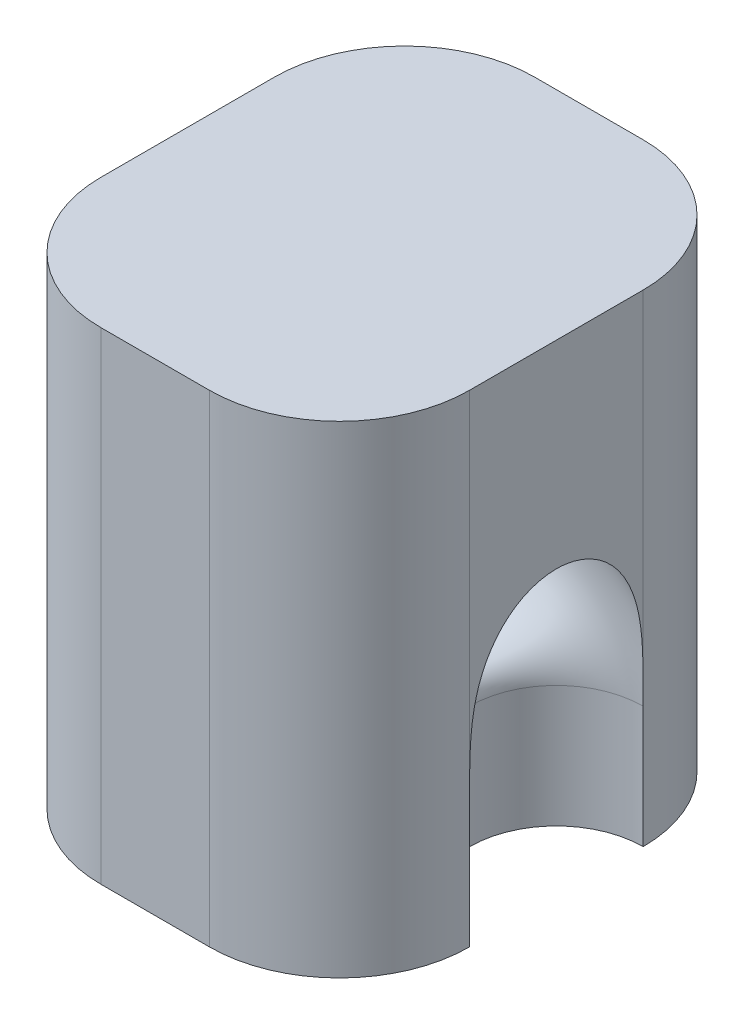
SolidWorks part; units mm, degrees
ref_plane "Front Plane" through (0, 0, 0) normal (0, 0, 1) x (1, 0, 0)
ref_plane "Top Plane" through (0, 0, 0) normal (0, 1, 0) x (1, 0, 0)
ref_plane "Right Plane" through (0, 0, 0) normal (1, 0, 0) x (0, 0, -1)
sketch "Sketch1" plane through (0, 0, 0) normal (0, 0, 1) x (1, 0, 0)
  line L4 (0, 0) -> (45, 0)
  line L5 (0, 0) -> (0, 11.1125)
  line L6 (0, 11.1125) -> (45, 11.1125) construction
  line L9 (15, 16.1125) -> (15, 11.1125) construction
  line L10 (30, 16.1125) -> (30, 11.1125) construction
  line L11 (0, 11.1125) -> (10, 11.1125)
  line L12 (35, 11.1125) -> (45, 11.1125)
  line L13 (45, 11.1125) -> (45, 0)
  spline S0 degree 3 poles (10, 11.1125) (14.5766, 20.182) (30.4234, 20.182) (35, 11.1125) knots 0 0 0 0 1 1 1 1
  dimension "D5" = 5
  dimension "D1" = 10
  dimension "D2" = 10
  dimension "D3" = 25
  dimension "D4" = 11.1125
  dimension "D6" = 5
  dimension "D7" = 5
extrude "Boss-Extrude1" add sketch "Sketch1" against normal blind 10
sketch "Sketch2" plane through (0, 0, 0) normal (0, 0, 1) x (1, 0, 0)
  line L0 (0, 0) -> (45, 0) construction
  line L2 (10, 11.1125) -> (10, 0) construction
  line L3 (10, 0) -> (35, 0) construction
  line L4 (35, 11.1125) -> (35, 0) construction
  line L5 (33, 10.6109) -> (33, 0)
  line L6 (12, 10.6109) -> (12, 0)
  spline S0 degree 3 poles (-1884.251, -531.3416) (2112.7694, 200.999) (-2067.7633, 201) (1929.2342, -531.3385) knots -3.992988 -3.992988 -3.992988 -3.992988 4.992976 4.992976 4.992976 4.992976 only from (35, 11.1125) to (10, 11.1125) construction
  spline S1 degree 3 poles (35, 11.1125) (30.4234, 20.182) (14.5766, 20.182) (10, 11.1125) knots 0 0 0 0 1 1 1 1 construction
  spline S2 degree 1 poles (33, 10.6109) (12, 10.6109) knots 0 0 1 1 construction
  spline S3 degree 3 poles (33, 10.6109) (32.5185, 11.4554) (31.2713, 12.9823) (27.9312, 15.2011) (22.5, 16.3903) (17.0688, 15.2011) (13.7287, 12.9823) (12.4815, 11.4554) (12, 10.6109) knots 0.018308 0.018308 0.018308 0.018308 0.138731 0.259154 0.5 0.740846 0.861269 0.981692 0.981692 0.981692 0.981692
  dimension "D1" = 2
extrude "Cut-Extrude2" cut sketch "Sketch2" against normal through all both and the other way through all
sketch "Sketch3" plane through (12, 0, 0) normal (1, 0, 0) x (0, 0, -1)
  line L0 (10, 10.6109) -> (0, 0) construction
  circle A0 centre (5, 5.3055) radius 2.5
  dimension "D1" = 5
extrude "Cut-Extrude3" cut sketch "Sketch3" against normal blind 6
sketch "Sketch4" plane through (6, 0, 0) normal (1, 0, 0) x (0, 0, -1)
  line L0 (2.5, 5.3055) -> (7.5, 5.3055) construction
  line L1 (5, 2.8055) -> (5, 7.8055) construction
  line L2 (5, 2.8055) -> (7.5, 2.8055) construction
  circle A0 centre (5, 5.3055) radius 2.5 construction
  circle A1 centre (5, 5.3055) radius 2
  dimension "D1" = 4
revolve "Cut-Revolve1" cut sketch "Sketch4" angle 90 about L2
sketch "Sketch5" plane through (0, 2.8055, 0) normal (0, 1, 0) x (1, 0, 0)
  circle A0 centre (3.5, 5) radius 2 construction
  circle A1 centre (3.5, 5) radius 2
extrude "Cut-Extrude4" cut sketch "Sketch5" against normal up to surface (2.8055 mm away) up to face at (6, 0, -5)
ref_plane "Plane1" through (22.5, 0, 0) normal (1, 0, 0) x (0, 0, -1)
mirror "Mirror1" about plane through (22.5, 0, 0) normal (1, 0, 0) of "Cut-Extrude4", "Cut-Revolve1", "Cut-Extrude3"
fillet "Fillet1" radius 5 4 edges at (10, 11.1125, -5) (35, 11.1125, -5) (33, 10.6109, -5) (12, 10.6109, -5)
sketch "Sketch6" plane through (0, 0, 0) normal (-1, 0, 0) x (0, 0, 1)
  line L0 (-10, 0) -> (0, 0)
  line L1 (-10, 0) -> (-10, 29.6855)
  line L2 (0, 0) -> (0, 29.6855)
  line L3 (-10, 29.6855) -> (0, 29.6855)
extrude "Cut-Extrude5" cut sketch "Sketch6" against normal up to surface (33 mm away) up to face at (33, 7.8055, -5)
sketch "Sketch7" plane through (0, 11.1125, 0) normal (0, 1, 0) x (1, 0, 0)
  line L1 (45, 0) -> (45, 10)
  line L2 (45, 0) -> (25.2323, 0)
  line L3 (45, 10) -> (25.2323, 10)
  line L4 (25.2323, 0) -> (25.2323, 10)
extrude "Cut-Extrude6" cut sketch "Sketch7" along normal through all
sketch "Sketch8" plane through (0, 0, 0) normal (0, -1, 0) x (1, 0, 0)
  line L0 (41.5, -10) -> (45, -10)
  line L1 (41.5, -10) -> (41.5, 1.2109)
  line L2 (45, -10) -> (45, 1.2109)
  line L3 (41.5, 1.2109) -> (45, 1.2109)
  line L4 (33, -10) -> (45, -10) construction
  point P0 (40.6945, 1.2109)
extrude "Cut-Extrude7" cut sketch "Sketch8" against normal through all
fillet "Fillet2" radius 3 4 edges at (33, 5.5563, -10) (33, 5.5563, 0) (41.5, 5.5563, -10) (41.5, 5.5563, 0)
